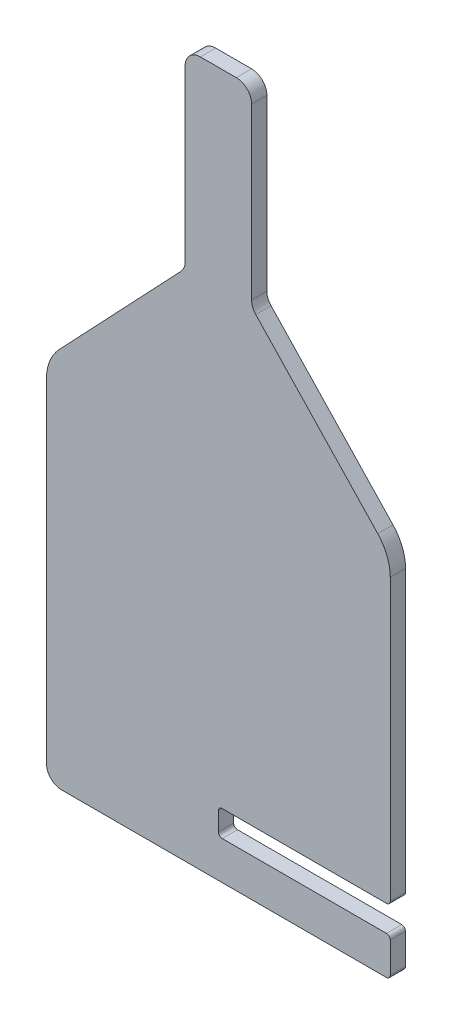
SolidWorks part; units mm, degrees
ref_plane "Alzado" through (0, 0, 0) normal (0, 0, 1) x (1, 0, 0)
ref_plane "Planta" through (0, 0, 0) normal (0, 1, 0) x (1, 0, 0)
ref_plane "Vista lateral" through (0, 0, 0) normal (1, 0, 0) x (0, 0, -1)
sketch "Croquis1" plane through (0, 0, 0) normal (0, 0, 1) x (1, 0, 0)
  line L0 (-4.35, 20) -> (-22.5, 0.8287)
  line L1 (-4.35, 45) -> (4.35, 45)
  line L2 (-22.5, 0.8287) -> (-22.5, -47.1713)
  line L3 (-22.5, -47.1713) -> (22.5, -47.1713)
  line L4 (22.5, 0.8287) -> (22.5, -47.1713)
  line L5 (-4.35, 45) -> (4.35, 45)
  line L6 (-4.35, 45) -> (-4.35, 20)
  line L8 (4.35, 45) -> (4.35, 19.999)
  line L9 (4.35, 19.999) -> (22.5, 0.8287)
  line L10 (0, 72.8664) -> (0, -82.626) construction
  dimension "D1" = 45
  dimension "D2" = 25
  dimension "D3" = 4.35
  dimension "D4" = 22.5
  dimension "D5" = 45
  dimension "D6" = 4.35
  dimension "D7" = 26.3993
  dimension "D8" = 26.4
  dimension "D9" = 48
  dimension "D10" = 48
extrude "Saliente-Extruir1" add sketch "Croquis1" along normal blind 2 contours L6 L0 L2 L3 L4 L9 L8 L1
sketch "Croquis3" plane through (0, 0, 2) normal (0, 0, 1) x (1, 0, 0)
  line L0 (22.5, 0.8287) -> (22.5, -47.1713) construction
  line L1 (22.5, -38.7713) -> (0, -38.7713)
  line L2 (22.5, -38.7713) -> (22.5, -42.1713)
  line L3 (22.5, -42.1713) -> (0, -42.1713)
  line L4 (0, -38.7713) -> (0, -42.1713)
  line L5 (-22.5, -47.1713) -> (22.5, -47.1713) construction
  dimension "D1" = 3.4
  dimension "D2" = 5
  dimension "D3" = 22.5
extrude "Cortar-Extruir2" cut sketch "Croquis3" against normal up to surface (2 mm away) up to face at (0, 4.6642, 0)
fillet "Redondeo1" radius 2 5 edges at (-22.5, -47.1713, 1) (-4.35, 20, 1) (-4.35, 45, 1) (4.35, 19.999, 1) (4.35, 45, 1)
fillet "Redondeo2" radius 6 2 edges at (-22.5, 0.8287, 1) (22.5, 0.8287, 1)
fillet "Redondeo3" radius 0.5 5 edges at (0, -42.1713, 1) (0, -38.7713, 1) (22.5, -42.1713, 1) (22.5, -38.7713, 1) (22.5, -47.1713, 1)
